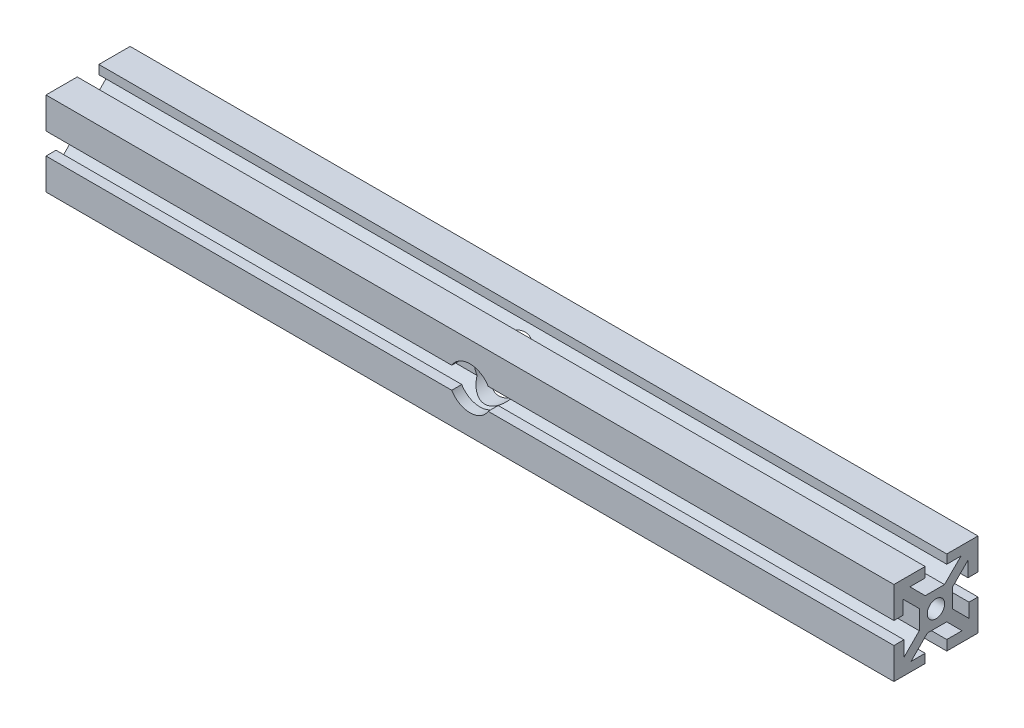
SolidWorks part; units mm, degrees
material "6061 Alloy"
ref_plane "Front Plane" through (0, 0, 0) normal (0, 0, 1) x (1, 0, 0)
ref_plane "Top Plane" through (0, 0, 0) normal (0, 1, 0) x (1, 0, 0)
ref_plane "Right Plane" through (0, 0, 0) normal (1, 0, 0) x (0, 0, -1)
sketch "Sketch1" plane through (0, 0, 0) normal (1, 0, 0) x (0, 0, -1)
  line L0 (2.5534, 5) -> (7.4749, 9.9215)
  line L1 (-5, 5) -> (5, 5)
  line L2 (-5, 5) -> (-5, -5)
  line L3 (-5, -5) -> (5, -5)
  line L4 (5, 5) -> (5, -5)
  line L5 (-5, 5) -> (5, -5) construction
  line L6 (-5, -5) -> (5, 5) construction
  line L7 (7.4749, 9.9215) -> (9.5962, 7.8001)
  line L8 (9.5962, 7.8001) -> (5, 3.2039)
  line L9 (5, 5) -> (13.6489, 13.6489) construction
  line L10 (7.4749, 9.9215) -> (3.24, 9.9215)
  line L11 (3.24, 9.9215) -> (3.24, 12.5962)
  line L12 (3.24, 12.5962) -> (12.5962, 12.5962)
  line L13 (9.5962, 7.8001) -> (9.5962, 3.24)
  line L14 (9.5962, 3.24) -> (12.5962, 3.24)
  line L15 (12.5962, 3.24) -> (12.5962, 12.5962)
  line L17 (0, 0) -> (0, 24.089) construction
  line L18 (0, 0) -> (23.75, 0) construction
  circle A0 centre (0, 0) radius 2.605
  point P0 (0, 0)
  dimension "D1" = 5.21
  dimension "D2" = 10
  dimension "D3" = 10
  dimension "D4" = 3
  dimension "D5" = 1.27
  dimension "D6" = 6.5
  dimension "D7" = 3.24
  dimension "D8" = 3.24
  dimension "D9" = 3
extrude "Boss-Extrude1" add sketch "Sketch1" along normal blind 254 contours L4 L1 L2 L3 A0 | L8 L7 L0 L1 L4 | L14 L15 L12 L11 L10 L7 L13 region at (0, 4.8586, -3.7767) region at (0, 6.7479, -6.3823) region at (0, 9.18, -9.3105)
ref_axis "Axis1" through (0, 0, 0) along (1, 0, 0)
pattern_circular "CirPattern1" count 4 over 360 about axis through (0, 0, 0) along (1, 0, 0) of "Boss-Extrude1"
sketch "Sketch2" plane through (0, 0, 12.5962) normal (0, 0, 1) x (1, 0, 0)
  circle A0 centre (127, 0) radius 6.35
  dimension "D1" = 12.7
  dimension "D2" = 127
extrude "Cut-Extrude1" cut sketch "Sketch2" against normal blind 30
